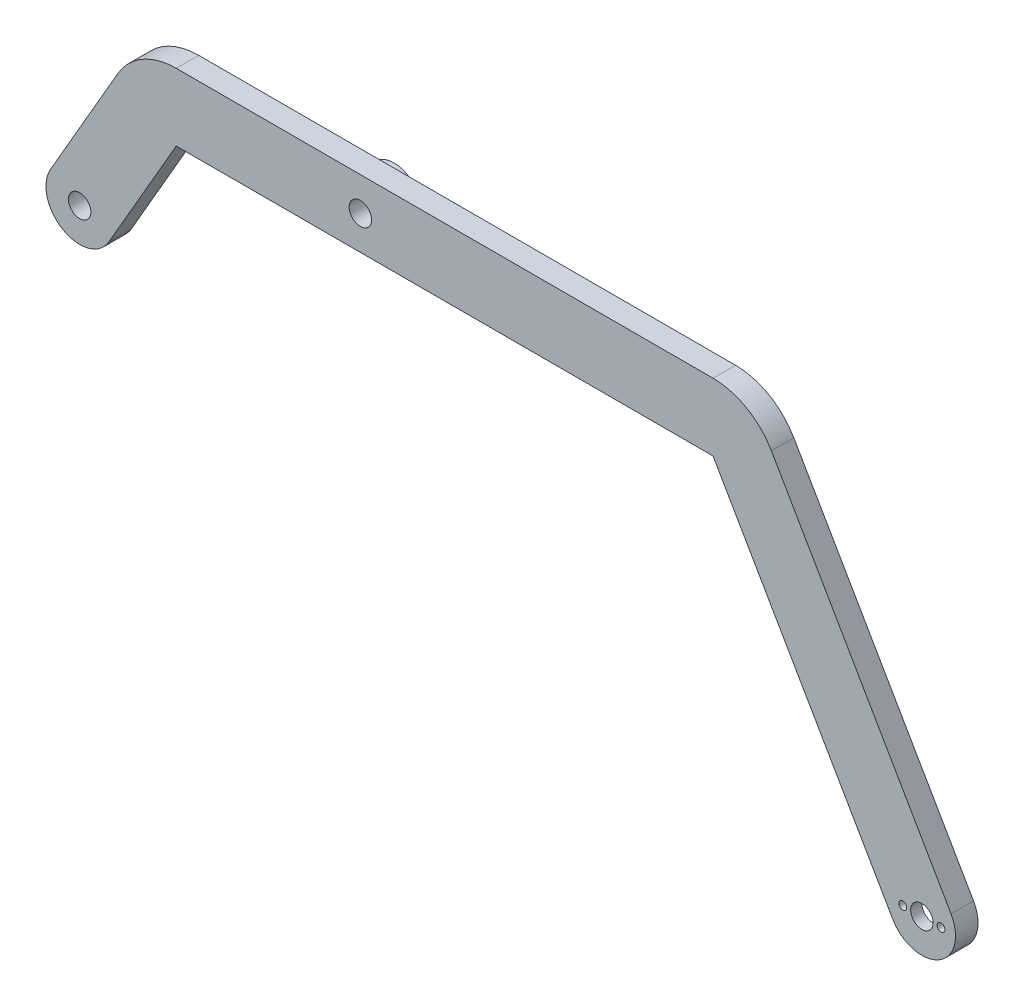
SolidWorks part; units mm, degrees
ref_plane "Front Plane" through (0, 0, 0) normal (0, 0, 1) x (1, 0, 0)
ref_plane "Top Plane" through (0, 0, 0) normal (0, 1, 0) x (1, 0, 0)
ref_plane "Right Plane" through (0, 0, 0) normal (1, 0, 0) x (0, 0, -1)
sketch "Sketch1" plane through (0, 0, 0) normal (0, 0, 1) x (1, 0, 0)
  line L0 (0, -15) -> (0, 15) construction
  line L4 (-82.0096, -15) -> (-112.0096, -66.9615)
  line L6 (-137.9904, -51.9615) -> (-107.9904, 0)
  line L7 (262.9904, -138.5641) -> (182.9904, 0)
  line L9 (157.0096, -15) -> (237.0096, -153.5641)
  line L10 (0, 15) -> (157.0096, 15)
  line L11 (0, -15) -> (157.0096, -15)
  line L12 (0, 15) -> (-82.0096, 15)
  line L13 (0, -15) -> (-82.0096, -15)
  line L14 (237.0096, -153.5641) -> (262.9904, -138.5641) construction
  line L15 (-137.9904, -51.9615) -> (-112.0096, -66.9615) construction
  arc A1 (-107.9904, 0) -> (-82.0096, 15) centre (-82.0096, -15) cw
  arc A2 (182.9904, 0) -> (157.0096, 15) centre (157.0096, -15) ccw
  arc A6 (237.0096, -153.5641) -> (262.9904, -138.5641) centre (250, -146.0641) ccw
  arc A7 (-137.9904, -51.9615) -> (-112.0096, -66.9615) centre (-125, -59.4615) ccw
  circle A8 centre (258.5, -146.0433) radius 1.75
  circle A9 centre (241.5, -146.0848) radius 1.75
  point P4 (0, 0)
  point P7 (0, -15)
  point P20 (0, 15)
  dimension "D2" = 60
  dimension "D6" = 3.5
  dimension "D7" = 3.5
  dimension "D1" = 30
  dimension "D3" = 250
  dimension "D4" = 160
  dimension "D5" = 125
extrude "Boss-Extrude1" add sketch "Sketch1" along normal blind 10
sketch "Sketch2" plane through (0, 0, 10) normal (0, 0, 1) x (1, 0, 0)
  circle A0 centre (-125, -59.4615) radius 5
  circle A1 centre (250, -146.0641) radius 5
  circle A2 centre (0, 0) radius 5
  dimension "D1" = 10
extrude "Cut-Extrude1" cut sketch "Sketch2" against normal up to surface (10 mm away) up to face at (260.25, -146.0433, 0)
sketch "Sketch3" plane through (0, 0, 0) normal (0, 0, -1) x (-1, 0, 0)
  circle A0 centre (0, 0) radius 12
extrude "Boss-Extrude2" add sketch "Sketch3" along normal blind 5
sketch "Sketch4" plane through (0, 0, 0) normal (0, 0, -1) x (-1, 0, 0)
  circle A0 centre (-250, -146.0641) radius 13
  dimension "D1" = 26
extrude "Cut-Extrude2" cut sketch "Sketch4" against normal offset from surface (5 mm away) 5 up to face at (-120, -59.4615, 10)
